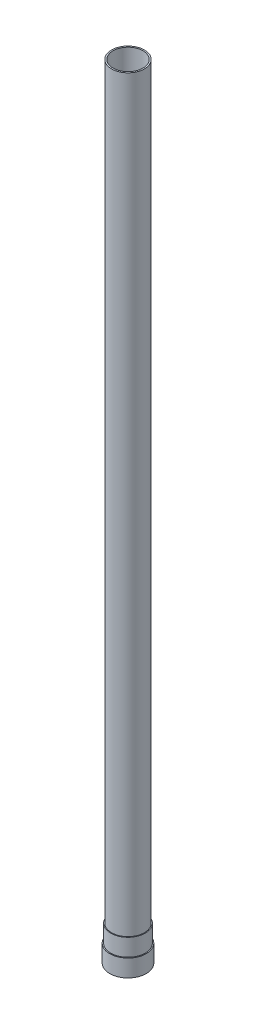
SolidWorks part; units mm, degrees
ref_plane "Front Plane" through (0, 0, 0) normal (0, 0, 1) x (1, 0, 0)
ref_plane "Top Plane" through (0, 0, 0) normal (0, 1, 0) x (1, 0, 0)
ref_plane "Right Plane" through (0, 0, 0) normal (1, 0, 0) x (0, 0, -1)
sketch "Sketch1" plane through (0, 0, 0) normal (0, 1, 0) x (1, 0, 0)
  circle A0 centre (0, 0) radius 15
  circle A1 centre (0, 0) radius 13.462
  circle A2 centre (0, 0) radius 15.875
  dimension "D1" = 30
  dimension "D2" = 31.75
  dimension "D3" = 2.413
extrude "Boss-Extrude1" add sketch "Sketch1" along normal blind 15 contours A0 A1 region at (-14.5757, 0, 0)
sketch "Sketch4" plane through (0, 15, 0) normal (0, 1, 0) x (1, 0, 0)
  circle A0 centre (0, 0) radius 14.2875
  circle A2 centre (0, 0) radius 13.0429
  point P4 (0, 0)
  circle M3 centre (0, 0) radius 13.462
  dimension "D1" = 28.575
  dimension "D2" = 1.2446
extrude "Boss-Extrude5" add sketch "Sketch4" along normal blind 650 contours A2 M3 | A0 M3 region at (-13.8834, 15, 0) region at (-13.0812, 15, 0)
extrude "Boss-Extrude6" add sketch "Sketch1<4>" against normal blind 15 contours A2 A0 | A0 A1 region at (-14.5757, 0, 0) region at (-15.426, 0, 0)
sketch "Sketch1<4>" plane through (0, 0, 0) normal (0, 1, 0) x (1, 0, 0) same geometry as "Sketch1"
equation "\"bottomheight\"= 15"
equation "\"D1@Boss-Extrude1\"=\"bottomheight\""
equation "\"topheight\" = 650"
equation "\"D1@Boss-Extrude5\"=\"topheight\""
equation "\"spacerheight\"=15"
equation "\"D1@Boss-Extrude6\"=\"spacerheight\""
